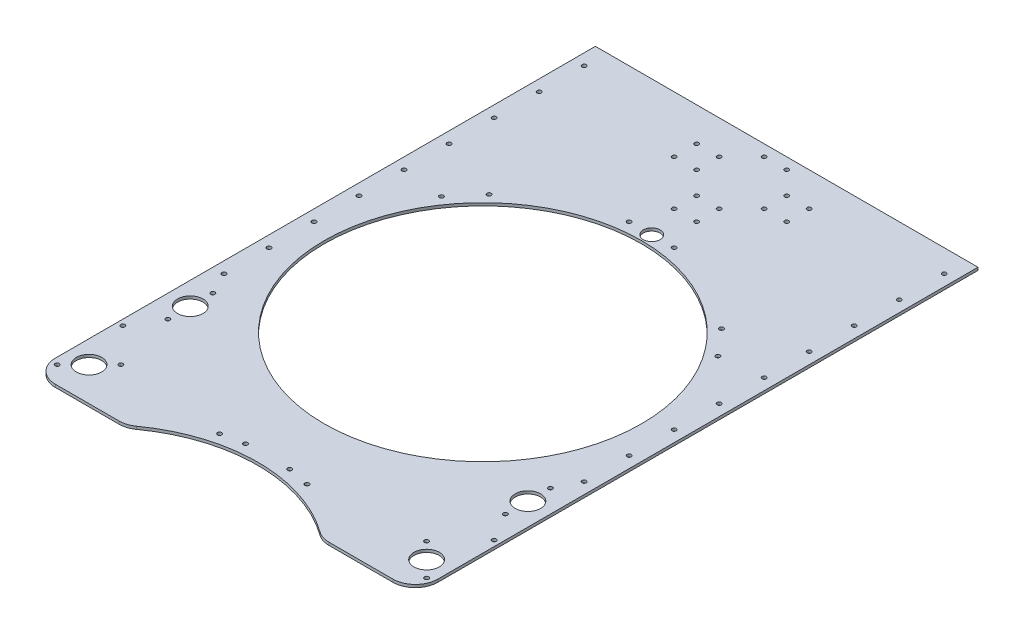
SolidWorks part; units mm, degrees
material "Thornel Mat VMA"
ref_plane "Front Plane" through (0, 0, 0) normal (0, 0, 1) x (1, 0, 0)
ref_plane "Top Plane" through (0, 0, 0) normal (0, 1, 0) x (1, 0, 0)
ref_plane "Right Plane" through (0, 0, 0) normal (1, 0, 0) x (0, 0, -1)
sketch "Sketch1" plane through (0, 0, 0) normal (0, 1, 0) x (1, 0, 0)
  line L1 (-215.9, 342.9) -> (215.9, 342.9)
  line L2 (-215.9, 342.9) -> (-215.9, -342.9)
  line L3 (-215.9, -342.9) -> (215.9, -342.9)
  line L4 (215.9, 342.9) -> (215.9, -342.9)
  line L5 (-215.9, 342.9) -> (215.9, -342.9) construction
  line L6 (-215.9, -342.9) -> (215.9, 342.9) construction
  point P0 (0, 0)
  dimension "D1" = 431.8
  dimension "D2" = 685.8
extrude "Boss-Extrude1" add sketch "Sketch1" along normal blind 3.175
sketch "Sketch2" plane through (0, 3.175, 0) normal (0, 1, 0) x (1, 0, 0)
  line L0 (0, -342.9) -> (0, 342.9) construction
  line L1 (-215.9, -342.9) -> (215.9, -342.9) construction
  line L2 (215.9, 342.9) -> (-215.9, 342.9) construction
  line L3 (-215.9, 342.9) -> (-215.9, -342.9) construction
  line L4 (-208.4605, -322.7605) -> (-190.5, -304.8) construction
  line L5 (-193.1461, -304.8) -> (-215.9, -304.8) construction
  circle A0 centre (-190.5, -304.8) radius 14.3129
  circle A1 centre (-190.5, -190.5) radius 14.3129
  circle A3 centre (190.5, -190.5) radius 14.3129
  circle A4 centre (190.5, -190.5) radius 25.4 construction
  circle A5 centre (-190.5, -190.5) radius 25.4 construction
  circle A6 centre (190.5, -215.9) radius 2.3813
  circle A7 centre (190.5, -165.1) radius 2.3813
  circle A8 centre (-190.5, -215.9) radius 2.3813
  circle A9 centre (-190.5, -165.1) radius 2.3813
  circle A10 centre (-190.5, -304.8) radius 25.4 construction
  circle A11 centre (-208.4605, -322.7605) radius 2.3813
  circle A15 centre (-172.5395, -286.8395) radius 2.3813
  circle A16 centre (172.5395, -286.8395) radius 2.3813
  circle A17 centre (208.4605, -322.7605) radius 2.3813
  circle A18 centre (190.5, -304.8) radius 14.3129
  point P33 (-190.5, -304.8)
  point P34 (-190.5, -304.8)
  dimension "D1" = 28.6258
  dimension "D2" = 28.6258
  dimension "D6" = 50.8
  dimension "D7" = 50.8
  dimension "D8" = 4.7625
  dimension "D9" = 4.7625
  dimension "D10" = 4.7625
  dimension "D11" = 4.7625
  dimension "D12" = 50.8
  dimension "D13" = 4.7625
  dimension "D3" = 38.1
  dimension "D4" = 114.3
  dimension "D5" = 25.4
  dimension "D15" = 45
  dimension "D14" = 2
extrude "Cut-Extrude1" cut sketch "Sketch2" against normal through all
sketch "Sketch3" plane through (0, 0, 0) normal (0, -1, 0) x (-1, 0, 0)
  line L1 (29.8706, 270.2084) -> (-24.7394, 270.2084)
  line L2 (29.8706, 270.2084) -> (29.8706, 216.2334)
  line L3 (29.8706, 216.2334) -> (-24.7394, 216.2334)
  line L4 (-24.7394, 270.2084) -> (-24.7394, 216.2334)
  line L5 (29.8706, 270.2084) -> (-24.7394, 216.2334) construction
  line L6 (29.8706, 216.2334) -> (-24.7394, 270.2084) construction
  point P0 (2.5656, 243.2209)
  dimension "D1" = 53.975
  dimension "D2" = 54.61
extrude "Boss-Extrude2" [suppressed] add sketch "Sketch3" along normal blind 203.2
fillet "Fillet1" [suppressed] radius 20.32
sketch "Sketch4" [suppressed] plane through (0, -203.2, 0) normal (0, -1, 0) x (-1, 0, 0)
  line L0 (-24.7394, 216.2334) -> (29.8706, 216.2334) construction
  line L1 (26.6956, 267.0334) -> (-21.5644, 267.0334)
  line L2 (26.6956, 267.0334) -> (26.6956, 219.4084)
  line L3 (26.6956, 219.4084) -> (-21.5644, 219.4084)
  line L4 (-21.5644, 267.0334) -> (-21.5644, 219.4084)
  line L5 (26.6956, 267.0334) -> (-21.5644, 219.4084) construction
  line L6 (26.6956, 219.4084) -> (-21.5644, 267.0334) construction
  line L7 (29.8706, 270.2084) -> (-24.7394, 270.2084) construction
  line L8 (29.8706, 216.2334) -> (29.8706, 270.2084) construction
  line L9 (-24.7394, 270.2084) -> (-24.7394, 216.2334) construction
  point P0 (2.5656, 243.2209)
  dimension "D1" = 3.175
  dimension "D2" = 3.175
  dimension "D3" = 3.175
  dimension "D4" = 3.175
extrude "Cut-Extrude2" [suppressed] cut sketch "Sketch4" against normal blind 203.2
sketch "Sketch5" [suppressed] plane through (-29.8706, 0, 0) normal (-1, 0, 0) x (0, 0, 1)
  line L0 (-216.2334, -203.2) -> (-216.2334, 0) construction
  line L1 (-216.2334, -203.2) -> (-270.2084, -203.2) construction
  circle A0 centre (-243.2209, -184.15) radius 14.2875
  dimension "D1" = 28.575
  dimension "D2" = 26.9875
  dimension "D3" = 19.05
extrude "Cut-Extrude3" [suppressed] cut sketch "Sketch5" against normal blind 203.2
sketch "Sketch6" plane through (0, 3.175, 0) normal (0, 1, 0) x (1, 0, 0)
  circle A0 centre (0, -50.8) radius 179.07
  dimension "D1" = 358.14
  dimension "D2" = 50.8
extrude "Cut-Extrude4" cut sketch "Sketch6" against normal through all
sketch "Sketch8" plane through (0, 3.175, 0) normal (0, 1, 0) x (1, 0, 0)
  circle A0 centre (0, 139.7) radius 9.525
  circle A2 centre (0, 139.7) radius 25.4 construction
  circle A3 centre (25.4, 139.7) radius 2.3813
  circle A4 centre (-25.4, 139.7) radius 2.3813
  dimension "D1" = 19.05
  dimension "D3" = 50.8
  dimension "D4" = 4.7625
  dimension "D5" = 4.7625
  dimension "D2" = 139.7
extrude "Cut-Extrude6" cut sketch "Sketch8" against normal through all
fillet "Fillet2" radius 25.4 2 edges at (215.9, 1.5875, 342.9) (-215.9, 1.5875, 342.9)
sketch "Sketch10" plane through (0, 3.175, 0) normal (0, 1, 0) x (1, 0, 0)
  line L0 (-215.9, 342.9) -> (-215.9, -317.5) construction
  line L1 (215.9, -317.5) -> (215.9, 342.9) construction
  circle A0 centre (-190.5, 215.9) radius 14.3129
  circle A1 centre (190.5, 215.9) radius 14.3129
  circle A2 centre (-190.5, 215.9) radius 25.4 construction
  circle A3 centre (190.5, 215.9) radius 25.4 construction
  circle A4 centre (190.5, 190.5) radius 2.3813
  circle A5 centre (190.5, 241.3) radius 2.3813
  circle A6 centre (-190.5, 190.5) radius 2.3813
  circle A7 centre (-190.5, 241.3) radius 2.3813
  circle A8 centre (190.5, -190.5) radius 14.3129 construction
  circle A9 centre (-190.5, -190.5) radius 14.3129 construction
  dimension "D1" = 28.6258
  dimension "D2" = 50.8
  dimension "D3" = 28.6258
  dimension "D4" = 50.8
  dimension "D5" = 4.7625
  dimension "D6" = 4.7625
  dimension "D7" = 4.7625
  dimension "D8" = 4.7625
  dimension "D9" = 25.4
  dimension "D10" = 25.4
  dimension "D11" = 406.4
  dimension "D12" = 406.4
extrude "Cut-Extrude8" [suppressed] cut sketch "Sketch10" against normal through all
sketch "Sketch11" plane through (0, 3.175, 0) normal (0, 1, 0) x (1, 0, 0)
  line L0 (0, -50.8) -> (156.0485, 58.4663) construction
  line L6 (0, 0) -> (0, 139.7) construction
  circle A0 centre (0, -50.8) radius 179.07
  circle A1 centre (0, -50.8) radius 179.07 construction
  circle A2 centre (0, -50.8) radius 184.15
  circle A3 centre (0, -50.8) radius 215.9
  circle A4 centre (156.0485, 58.4663) radius 2.3813
  circle A5 centre (131.1838, 87.3342) radius 2.3813
  circle A6 centre (0, -50.8) radius 190.5 construction
  circle A7 centre (-131.1838, 87.3342) radius 2.3813
  circle A8 centre (-156.0485, 58.4663) radius 2.3813
  dimension "D1" = 368.3
  dimension "D6" = 431.8
  dimension "D7" = 381
  dimension "D9" = 4.7625
  dimension "D10" = 4.7625
  dimension "D2" = 55
  dimension "D8" = 38.1
extrude "Cut-Extrude9" cut sketch "Sketch11" against normal through all contours A4 | A5 | A7 | A8 region at (156.0485, 3.175, -58.4663) region at (131.1838, 3.175, -87.3342) region at (-131.1838, 3.175, -87.3342) region at (-156.0485, 3.175, -58.4663)
sketch "Sketch13" plane through (0, 3.175, 0) normal (0, 1, 0) x (1, 0, 0)
  line L0 (-215.9, 342.9) -> (-215.9, -317.5) construction
  line L1 (215.9, 342.9) -> (-215.9, 342.9) construction
  line L2 (0, -342.9) -> (0, 342.9) construction
  line L3 (-190.5, -342.9) -> (190.5, -342.9) construction
  circle A0 centre (-203.2, 317.5) radius 2.3813
  circle A1 centre (-203.2, 266.7) radius 2.3813
  circle A2 centre (-203.2, 215.9) radius 2.3813
  circle A3 centre (-203.2, 165.1) radius 2.3813
  circle A4 centre (-203.2, 114.3) radius 2.3813
  circle A5 centre (-203.2, 63.5) radius 2.3813
  circle A6 centre (-203.2, 12.7) radius 2.3813
  circle A7 centre (-203.2, -38.1) radius 2.3813
  circle A8 centre (-203.2, -88.9) radius 2.3813
  circle A9 centre (-203.2, -139.7) radius 2.3813
  circle A10 centre (203.2, -139.7) radius 2.3813
  circle A11 centre (203.2, 12.7) radius 2.3813
  circle A12 centre (203.2, 63.5) radius 2.3813
  circle A13 centre (203.2, 114.3) radius 2.3813
  circle A14 centre (203.2, 165.1) radius 2.3813
  circle A15 centre (203.2, 266.7) radius 2.3813
  circle A16 centre (203.2, 317.5) radius 2.3813
  circle A17 centre (-25.4, -330.2) radius 2.4664
  circle A20 centre (-50.8, -330.2) radius 2.3078
  circle A21 centre (50.8, -330.2) radius 2.3078
  circle A22 centre (25.4, -330.2) radius 2.4664
  circle A23 centre (203.2, -88.9) radius 2.3813
  circle A24 centre (203.2, -38.1) radius 2.3813
  circle A25 centre (203.2, 215.9) radius 2.3813
  dimension "D1" = 4.7625
  dimension "D2" = 12.7
  dimension "D3" = 25.4
  dimension "D5" = 25.4
  dimension "D6" = 50.8
  dimension "D7" = 12.7
  dimension "D8" = 12.7
  dimension "D4" = 10
extrude "Cut-Extrude10" cut sketch "Sketch13" against normal through all
sketch "Sketch14" plane through (0, 3.175, 0) normal (0, 1, 0) x (1, 0, 0)
  line L0 (215.9, -317.5) -> (215.9, 342.9) construction
  line L1 (0, -342.9) -> (0, -229.87) construction
  line L2 (-190.5, -342.9) -> (190.5, -342.9) construction
  circle A0 centre (209.55, -247.65) radius 2.3813
  circle A2 centre (0, -50.8) radius 179.07 construction
  circle A3 centre (-209.55, -247.65) radius 2.3813
  circle A4 centre (190.5, -304.8) radius 14.3129 construction
  dimension "D1" = 57.15
  dimension "D3" = 4.7625
  dimension "D2" = 6.35
extrude "Cut-Extrude11" cut sketch "Sketch14" against normal through all
sketch "Sketch16" plane through (0, 3.175, 0) normal (0, 1, 0) x (1, 0, 0)
  line L0 (215.9, -317.5) -> (215.9, 342.9) construction
  line L1 (-215.9, 342.9) -> (215.9, 342.9)
  line L2 (-215.9, 342.9) -> (-215.9, 292.1)
  line L3 (-215.9, 292.1) -> (215.9, 292.1)
  line L4 (215.9, 342.9) -> (215.9, 292.1)
  dimension "D1" = 50.8
extrude "Cut-Extrude13" cut sketch "Sketch16" against normal through all
sketch "Sketch17" plane through (0, 0, 0) normal (0, -1, 0) x (-1, 0, 0)
  line L0 (0, -482.6) -> (0, 3.1553) construction
  line L1 (0, -482.6) -> (24.8652, -293.7298) construction
  line L2 (0, -482.6) -> (49.305, -298.5911) construction
  circle A0 centre (0, -482.6) radius 177.8
  circle A1 centre (0, -482.6) radius 190.5 construction
  circle A2 centre (24.8652, -293.7298) radius 2.3813
  circle A3 centre (49.305, -298.5911) radius 2.3813
  circle A4 centre (-24.8652, -293.7298) radius 2.3813
  circle A5 centre (-49.305, -298.5911) radius 2.3813
  dimension "D1" = 355.6
  dimension "D3" = 381
  dimension "D6" = 4.7625
  dimension "D7" = 4.7625
  dimension "D2" = 482.6
  dimension "D4" = 7.5
  dimension "D5" = 15
extrude "Cut-Extrude14" cut sketch "Sketch17" against normal through all
fillet "Fillet3" radius 25.4 2 edges at (109.9852, 1.5875, 342.9) (-109.9852, 1.5875, 342.9)
sketch "Sketch18" plane through (0, 3.175, 0) normal (0, 1, 0) x (1, 0, 0)
  line L0 (-215.9, 292.1) -> (215.9, 292.1) construction
  line L1 (25.4, 215.9) -> (-25.4, 215.9) construction
  line L2 (25.4, 215.9) -> (25.4, 266.7) construction
  line L3 (25.4, 266.7) -> (-25.4, 266.7) construction
  line L4 (-25.4, 215.9) -> (-25.4, 266.7) construction
  line L5 (25.4, 215.9) -> (-25.4, 266.7) construction
  line L6 (25.4, 266.7) -> (-25.4, 215.9) construction
  line L8 (25.4, 215.9) -> (76.2, 215.9) construction
  line L9 (25.4, 215.9) -> (25.4, 266.7) construction
  line L10 (25.4, 266.7) -> (76.2, 266.7) construction
  line L11 (76.2, 215.9) -> (76.2, 266.7) construction
  circle A0 centre (38.1, 228.6) radius 2.3812
  circle A1 centre (63.5, 228.6) radius 2.3813
  circle A2 centre (63.5, 254) radius 2.3813
  circle A3 centre (38.1, 254) radius 2.3813
  circle A4 centre (-12.7, 177.8) radius 2.3813
  circle A5 centre (-12.7, 203.2) radius 2.3813
  circle A6 centre (12.7, 177.8) radius 2.3813
  circle A7 centre (12.7, 203.2) radius 2.3812
  circle A8 centre (-63.5, 254) radius 2.3812
  circle A9 centre (-38.1, 254) radius 2.3813
  circle A10 centre (-63.5, 228.6) radius 2.3813
  circle A11 centre (-38.1, 228.6) radius 2.3813
  circle A12 centre (12.7, 304.8) radius 2.3812
  circle A13 centre (12.7, 279.4) radius 2.3812
  circle A14 centre (-12.7, 304.8) radius 2.3813
  circle A15 centre (-12.7, 279.4) radius 2.3812
  point P0 (0, 241.3)
  point P45 (0, 241.3)
  dimension "D5" = 4.7625
  dimension "D1" = 50.8
  dimension "D2" = 50.8
  dimension "D3" = 50.8
  dimension "D4" = 12.7
  dimension "D6" = 25.4
  dimension "D9" = 50.8
  dimension "D10" = 4
  dimension "D7" = 2
  dimension "D8" = 2
extrude "Cut-Extrude15" cut sketch "Sketch18" against normal through all
